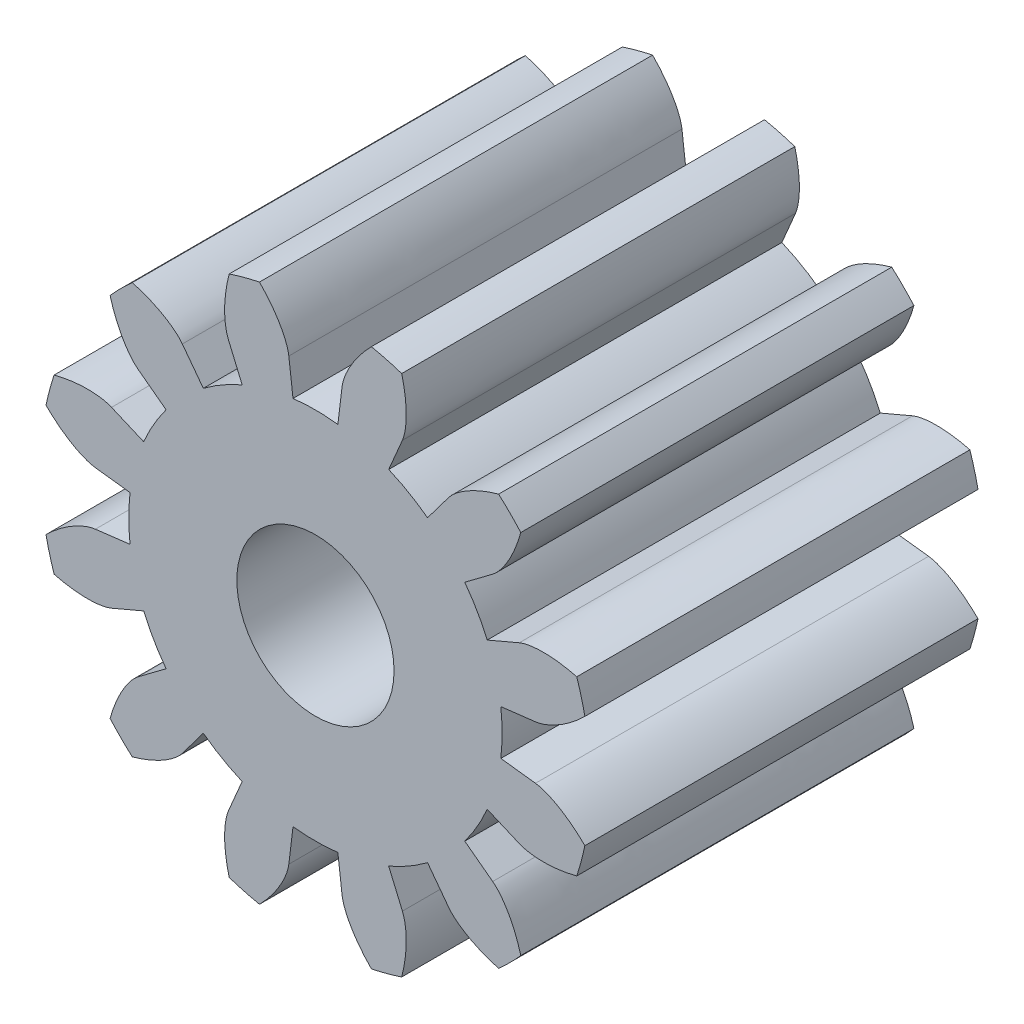
SolidWorks part; units mm, degrees
ref_plane "前视基准面" through (0, 0, 0) normal (0, 0, 1) x (1, 0, 0)
ref_plane "上视基准面" through (0, 0, 0) normal (0, 1, 0) x (1, 0, 0)
ref_plane "右视基准面" through (0, 0, 0) normal (1, 0, 0) x (0, 0, -1)
other "Configuration Table"
sketch "草图1" plane through (0, 0, 0) normal (0, 0, 1) x (1, 0, 0)
  line L0 (0, 0) -> (3, 0) construction
  line L1 (0, 0) -> (2.9743, 0.3916) construction
  line L2 (0, 0) -> (2.7987, 0.3386)
  line L3 (2.9743, 0.3916) -> (2.9743, -0.3916) construction
  line L4 (0, 0) -> (2.7987, -0.3386)
  circle A0 centre (0, 0) radius 3.5
  circle A1 centre (0, 0) radius 3 construction
  circle A2 centre (0, 0) radius 2.375
  circle A3 centre (0, 0) radius 2.8191 construction
  circle A4 centre (0, 0) radius 1
  spline S0 degree 4 poles (2.7987, 0.3386) (2.82, 0.3411) (2.879, 0.3528) (2.9873, 0.3924) (3.1523, 0.4801) (3.3463, 0.6259) (3.5662, 0.8464) (3.7825, 1.1408) (3.9711, 1.4947) (4.1197, 1.9006) (4.217, 2.3214) (4.2662, 2.7504) (4.2704, 3.2034) (4.2171, 3.7619) (4.0685, 4.4153) (3.7871, 5.1414) (3.3531, 5.89) (2.817, 6.5681) (2.1934, 7.1673) (1.5005, 7.6821) (0.7472, 8.1086) (-0.0448, 8.4455) (-0.8785, 8.6913) (-1.6117, 8.8286) (-2.2718, 8.8897) (-2.746, 8.9054) (-3.1682, 8.8973) (-3.4474, 8.8817) (-3.8403, 8.8483) (-4.1356, 8.8059) (-4.4307, 8.7603) (-4.5782, 8.7282) (-4.6735, 8.7099) knots 0 0 0 0 0 0.005604 0.015718 0.02996 0.048734 0.068727 0.096889 0.125051 0.153212 0.181374 0.209535 0.237696 0.271429 0.327752 0.384075 0.440398 0.496721 0.553044 0.609367 0.66569 0.722013 0.778336 0.834659 0.86282 0.890982 0.909091 0.931818 0.954545 0.977273 1 1 1 1 1 construction
  spline S1 degree 4 poles (2.7987, 0.3386) (2.82, 0.3411) (2.879, 0.3528) (2.9873, 0.3924) (3.1523, 0.4801) (3.3463, 0.6259) (3.5662, 0.8464) (3.7825, 1.1408) (3.9711, 1.4947) (4.1197, 1.9006) (4.217, 2.3214) (4.2662, 2.7504) (4.2704, 3.2034) (4.2171, 3.7619) (4.0685, 4.4153) (3.7871, 5.1414) (3.3531, 5.89) (2.817, 6.5681) (2.1934, 7.1673) (1.5005, 7.6821) (0.7472, 8.1086) (-0.0448, 8.4455) (-0.8785, 8.6913) (-1.6117, 8.8286) (-2.2718, 8.8897) (-2.746, 8.9054) (-3.0694, 8.8992) (-3.2301, 8.8926) (-3.293, 8.8894) knots 0 0 0 0 0 0.005604 0.015718 0.02996 0.048734 0.068727 0.096889 0.125051 0.153212 0.181374 0.209535 0.237696 0.271429 0.327752 0.384075 0.440398 0.496721 0.553044 0.609367 0.66569 0.722013 0.778336 0.834659 0.86282 0.890982 0.909091 0.909091 0.909091 0.909091 0.909091
  spline S2 degree 4 poles (2.7987, -0.3386) (2.82, -0.3411) (2.879, -0.3528) (2.9873, -0.3924) (3.1523, -0.4801) (3.3463, -0.6259) (3.5662, -0.8464) (3.7825, -1.1408) (3.9711, -1.4947) (4.1197, -1.9006) (4.217, -2.3214) (4.2662, -2.7504) (4.2704, -3.2034) (4.2171, -3.7619) (4.0685, -4.4153) (3.7871, -5.1414) (3.3531, -5.89) (2.817, -6.5681) (2.1934, -7.1673) (1.5005, -7.6821) (0.7472, -8.1086) (-0.0448, -8.4455) (-0.8785, -8.6913) (-1.6117, -8.8286) (-2.2718, -8.8897) (-2.746, -8.9054) (-3.1682, -8.8973) (-3.4474, -8.8817) (-3.8403, -8.8483) (-4.1356, -8.8059) (-4.4307, -8.7603) (-4.5782, -8.7282) (-4.6735, -8.7099) knots 0 0 0 0 0 0.005604 0.015718 0.02996 0.048734 0.068727 0.096889 0.125051 0.153212 0.181374 0.209535 0.237696 0.271429 0.327752 0.384075 0.440398 0.496721 0.553044 0.609367 0.66569 0.722013 0.778336 0.834659 0.86282 0.890982 0.909091 0.931818 0.954545 0.977273 1 1 1 1 1 construction
  spline S3 degree 4 poles (2.7987, -0.3386) (2.82, -0.3411) (2.879, -0.3528) (2.9873, -0.3924) (3.1523, -0.4801) (3.3463, -0.6259) (3.5662, -0.8464) (3.7825, -1.1408) (3.9711, -1.4947) (4.1197, -1.9006) (4.217, -2.3214) (4.2662, -2.7504) (4.2704, -3.2034) (4.2171, -3.7619) (4.0685, -4.4153) (3.7871, -5.1414) (3.3531, -5.89) (2.817, -6.5681) (2.1934, -7.1673) (1.5005, -7.6821) (0.7472, -8.1086) (-0.0448, -8.4455) (-0.8785, -8.6913) (-1.6117, -8.8286) (-2.2718, -8.8897) (-2.746, -8.9054) (-3.0694, -8.8992) (-3.2301, -8.8926) (-3.293, -8.8894) knots 0 0 0 0 0 0.005604 0.015718 0.02996 0.048734 0.068727 0.096889 0.125051 0.153212 0.181374 0.209535 0.237696 0.271429 0.327752 0.384075 0.440398 0.496721 0.553044 0.609367 0.66569 0.722013 0.778336 0.834659 0.86282 0.890982 0.909091 0.909091 0.909091 0.909091 0.909091
  point P15 (2.9743, 0)
  dimension "齿顶圆直径" = 7
  dimension "分度圆直径" = 6
  dimension "齿根圆直径" = 4.75
  dimension "基圆直径" = 5.6382
  dimension "内孔直径" = 2
  dimension "渐近线镜像线夹角" = 7.5
extrude "凸台-拉伸1" add sketch "草图1" along normal blind 5 contours A0 | A4
extrude "切除-拉伸1" cut sketch "草图1<3>" along normal through all contours A2 S3 A0 S1 region at (3.0158, 0, 0)
sketch "草图1<3>" plane through (0, 0, 0) normal (0, 0, 1) x (1, 0, 0) same geometry as "草图1"
pattern_circular "阵列(圆周)1" count 12 every 30 about axis through (0, 0, 5) along (0, 0, 1) of "切除-拉伸1"
equation "\"m\"= 0.5'模数"
equation "\"z\" = 12'齿数"
equation "\"a\"= 20度'压力角"
equation "\"d\"= \"m\" * \"z\"'分度圆直径"
equation "\"da\"= ( \"z\" + 2 ) * \"m\"'齿顶圆直径"
equation "\"df\"= ( \"z\" - 2.5 ) * \"m\"'齿根圆直径"
equation "\"s\"= 0.5 * PI * \"m\"'分度圆齿厚"
equation "\"r\"= 0.38 * \"m\"'齿根圆角"
equation "\"B\"= 0.3 * \"d\"'齿厚"
equation "\"db\"= \"m\" * \"z\" * cos ( \"a\" )'基圆直径"
equation "\"rb\"= \"db\" / 2'基圆半径"
equation "\"齿顶圆直径@草图1\"= \"da\""
equation "\"分度圆直径@草图1\"= \"d\""
equation "\"齿根圆直径@草图1\"= \"df\""
equation "\"基圆直径@草图1\"= \"db\""
equation "\"渐近线镜像线夹角@草图1\"= 360 / 4 / \"z\""
equation "\"h\"= 5'齿轮厚度"
equation "\"ir\"= 2'内孔直径"
equation "\"内孔直径@草图1\"= \"ir\""
equation "\"齿轮厚@凸台-拉伸1\"= \"h\""
equation "\"齿轮夹角@阵列(圆周)1\"= 360 / \"z\""
equation "\"齿数@阵列(圆周)1\"= \"z\""
